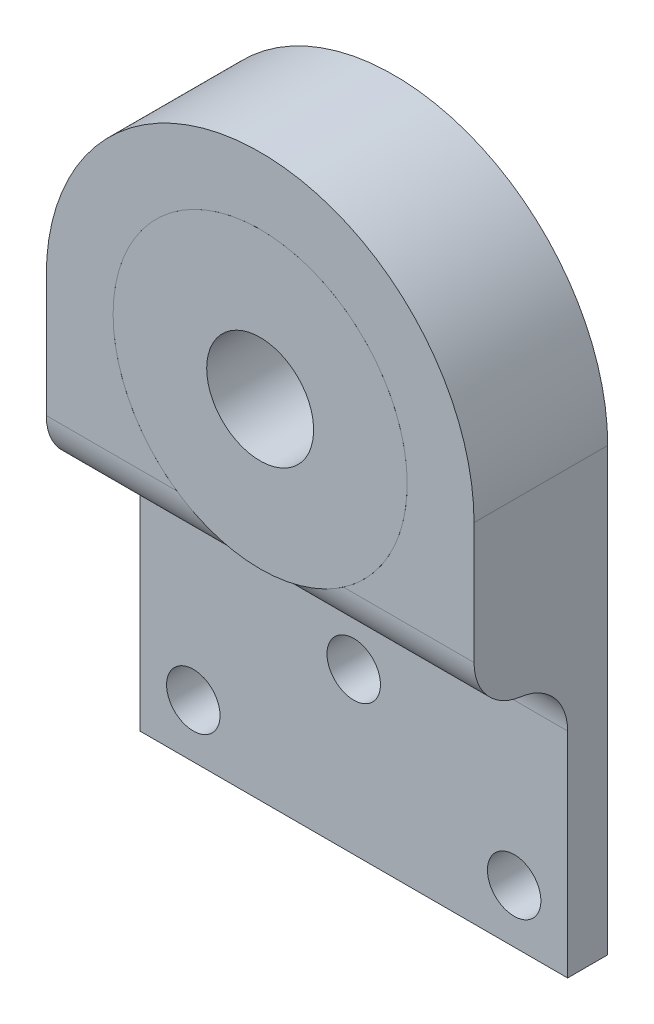
SolidWorks part; units mm, degrees
ref_plane "Front Plane" through (0, 0, 0) normal (0, 0, 1) x (1, 0, 0)
ref_plane "Top Plane" through (0, 0, 0) normal (0, 1, 0) x (1, 0, 0)
ref_plane "Right Plane" through (0, 0, 0) normal (1, 0, 0) x (0, 0, -1)
sketch "Sketch1" plane through (0, 0, 0) normal (0, 0, 1) x (1, 0, 0)
  line L0 (-11, 0) -> (11, 0) construction
  line L1 (0, -11) -> (-11.619, -11) construction
  line L6 (-16, 0) -> (-11, 0) construction
  line L7 (-16, 0) -> (-16, -13)
  line L8 (-16, -13) -> (16, -13)
  line L9 (16, 0) -> (16, -13)
  line L10 (11, 0) -> (16, 0) construction
  circle A0 centre (0, 0) radius 11
  arc A1 (-7.0204, -14.3776) -> (7.0204, -14.3776) centre (0, 0) ccw construction
  arc A2 (-10.3435, -12.2071) -> (-9.3274, -13) centre (0, 0) ccw construction
  circle A3 centre (0, 0) radius 16 construction
  arc A4 (9.3274, -13) -> (10.3435, -12.2071) centre (0, 0) ccw construction
  arc A5 (16, 0) -> (-16, 0) centre (0, 0) ccw
  arc A6 (-9.3274, -13) -> (-7.0204, -14.3776) centre (0, 0) ccw construction
  arc A7 (7.0204, -14.3776) -> (9.3274, -13) centre (0, 0) ccw construction
  arc A8 (10.3435, -12.2071) -> (16, 0) centre (0, 0) ccw construction
  arc A9 (-16, 0) -> (-11.619, -11) centre (0, 0) ccw construction
  arc A10 (-11.619, -11) -> (-10.3435, -12.2071) centre (0, 0) ccw construction
  point P7 (0, -13.5)
  dimension "D1" = 22
  dimension "D3" = 13
  dimension "D2" = 5
extrude "Boss-Extrude1" add sketch "Sketch1" along normal blind 10
sketch "Sketch2" plane through (0, 0, 0) normal (0, 0, -1) x (-1, 0, 0)
  circle A0 centre (0, 0) radius 11 construction
  circle A1 centre (0, 0) radius 11
  circle A2 centre (0, 0) radius 4
  dimension "D1" = 7
extrude "Boss-Extrude2" add sketch "Sketch2" against normal blind 10 separate body
sketch "Sketch3" plane through (0, 0, 0) normal (0, 0, -1) x (-1, 0, 0)
  line L0 (16, 0) -> (16, -13) construction
  line L1 (-16, -13) -> (16, -13)
  line L2 (-16, -13) -> (-16, -33)
  line L3 (-16, -33) -> (16, -33)
  line L4 (16, -13) -> (16, -33)
  line L5 (0, -13) -> (0, -33) construction
  circle A0 centre (0, -21) radius 2
  circle A1 centre (12, -29) radius 2
  circle A2 centre (-12, -29) radius 2
  point P11 (0.1886, -21)
  point P12 (0, -21)
  dimension "D2" = 8
  dimension "D3" = 4
  dimension "D1" = 20
  dimension "D4" = 4
  dimension "D5" = 4
  dimension "D6" = 4
  dimension "D7" = 4
extrude "Boss-Extrude3" add sketch "Sketch3" against normal blind 3
fillet "Fillet2" radius 4 1 edges at (0, -13, 3)
fillet "Fillet3" radius 4 1 edges at (0, -13, 10)
sketch "Sketch4" [suppressed] plane through (0, 0, 0) normal (0, 0, -1) x (-1, 0, 0)
  circle A0 centre (0, 0) radius 13
  circle A1 centre (0, 0) radius 11
  circle A2 centre (0, 0) radius 11 construction
  circle A3 centre (0, 0) radius 9
  dimension "D1" = 0
  dimension "D2" = 2
  dimension "D3" = 2
sketch "Sketch5" plane through (0, 0, 0) normal (0, 0, -1) x (-1, 0, 0)
  circle A1 centre (0, 0) radius 11 construction
  circle A2 centre (0, 0) radius 13
  circle A3 centre (0, 0) radius 9
  dimension "D1" = 2
  dimension "D2" = 2
extrude "Boss-Extrude5" add sketch "Sketch5" against normal blind 1
